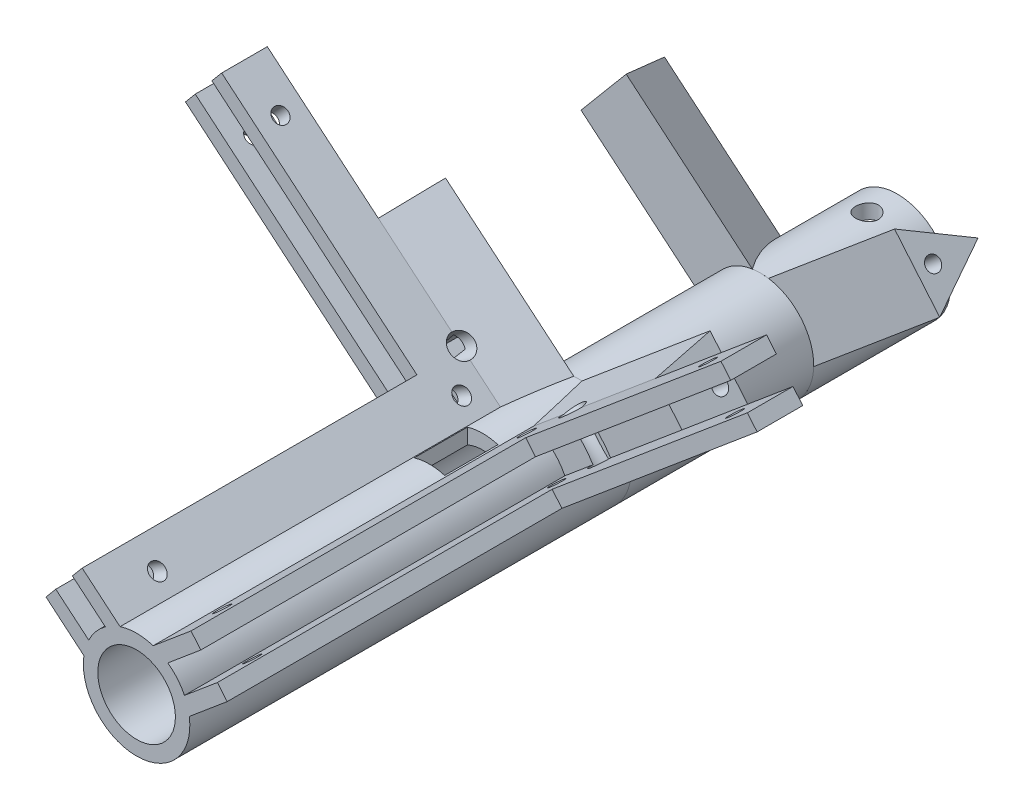
SolidWorks part; units mm, degrees
material "尼龙 101"
ref_plane "前视基准面" through (0, 0, 0) normal (0, 0, 1) x (1, 0, 0)
ref_plane "上视基准面" through (0, 0, 0) normal (0, 1, 0) x (1, 0, 0)
ref_plane "右视基准面" through (0, 0, 0) normal (1, 0, 0) x (0, 0, -1)
other "Configuration Table"
ref_plane "基准面1" through (0, 0, 10) normal (0, 0, 1) x (1, 0, 0)
sketch "草图1" plane through (0, 0, 10) normal (0, 0, 1) x (1, 0, 0)
  circle A0 centre (0, 0) radius 5.1
  circle A1 centre (0, 0) radius 7
  dimension "D1" = 10.2
  dimension "D2" = 14
extrude "凸台-拉伸1" add sketch "草图1" along normal blind 100
ref_plane "基准面2" through (0, 0, 20) normal (0, 0, 1) x (1, 0, 0)
sketch "草图2" plane through (0, 0, 20) normal (0, 0, 1) x (1, 0, 0)
  line L0 (0, -1000) -> (0, 49000) construction
  line L1 (766.0444, -642.7876) -> (-37536.1777, 31496.5929) construction
  line L2 (-766.0444, -642.7876) -> (37536.1777, 31496.5929) construction
  line L3 (0.5389, 6.9792) -> (17.3919, 21.1206)
  line L4 (6.9668, -0.6812) -> (23.8198, 13.4601)
  line L5 (17.3919, 21.1206) -> (23.8198, 13.4601)
  line L6 (-17.3919, 21.1206) -> (-23.8198, 13.4601)
  line L7 (-6.9668, -0.6812) -> (-23.8198, 13.4601)
  line L8 (-0.5389, 6.9792) -> (-17.3919, 21.1206)
  arc A0 (0.5389, 6.9792) -> (-0.5389, 6.9792) centre (0, 0) ccw
  arc A1 (-6.9668, -0.6812) -> (6.9668, -0.6812) centre (0, 0) ccw
  circle A2 centre (0, 0) radius 5.1
  dimension "D1" = 14
  dimension "D6" = 10.2
  dimension "D2" = 50
  dimension "D3" = 50
  dimension "D4" = 10
  dimension "D5" = 22
extrude "凸台-拉伸2" add sketch "草图2" along normal blind 40
ref_plane "基准面3" through (0, 0, 0) normal (-0.6428, 0.766, 0) x (0.766, 0.6428, 0)
sketch "草图4" plane through (0, 0, 0) normal (-0.6428, 0.766, 0) x (0.766, 0.6428, 0)
  line L0 (0, -1000) -> (0, 49000) construction
  line L1 (26.899, -60) -> (26.899, -20) construction
  line L2 (6.999, -28) -> (27.999, -28)
  line L3 (6.999, -28) -> (6.999, -52)
  line L4 (6.999, -52) -> (27.999, -52)
  line L5 (27.999, -28) -> (27.999, -52)
  line L6 (6.999, -28) -> (27.999, -52) construction
  line L7 (6.999, -52) -> (27.999, -28) construction
  point P1 (17.499, -40)
  point P11 (26.899, -40)
  dimension "D1" = 9.4
  dimension "D2" = 21
  dimension "D3" = 24
revolve "切除-旋转1" cut sketch "草图4" angle 360 about L0
sketch "草图5" plane through (20.6058, 17.2903, 0) normal (0.766, 0.6428, 0) x (0, 0, -1)
  circle A0 centre (-25.9, 0) radius 0.95
  circle A1 centre (-53.9, 0) radius 0.95
  dimension "D1" = 1.9
  dimension "D2" = 1.9
extrude "切除-拉伸1" cut sketch "草图5" against normal blind 5
chamfer "倒角1" distance 5 angle 60 4 edges at (-15.3933, 6.3894, 20) (-8.9654, 14.0499, 20) (8.9654, 14.0499, 20) (15.3933, 6.3894, 20) first distance on face at (-12.5817, 10.5573, 20) first distance on face at (12.5817, 10.5573, 20)
sketch "草图7" plane through (0, 0, 60) normal (0, 0, 1) x (1, 0, 0)
  line L0 (8.1483, 9.5786) -> (10.848, 6.3612)
  line L1 (10.848, 6.3612) -> (12.1503, 7.454)
  line L2 (12.1503, 7.454) -> (9.4506, 10.6713)
  line L3 (9.4506, 10.6713) -> (8.1483, 9.5786)
  line L4 (-12.1503, 7.454) -> (-9.4506, 10.6713)
  line L5 (6.9668, -0.6812) -> (23.8198, 13.4601) construction
  line L6 (23.8198, 13.4601) -> (17.3919, 21.1206) construction
  line L7 (0, -1000) -> (0, 49000) construction
  line L8 (-10.848, 6.3612) -> (-12.1503, 7.454)
  line L9 (-8.1483, 9.5786) -> (-10.848, 6.3612)
  line L10 (-9.4506, 10.6713) -> (-8.1483, 9.5786)
  dimension "D1" = 4.2
  dimension "D2" = 1.7
  dimension "D3" = 2.9
  dimension "D4" = 12.8
extrude "切除-拉伸2" cut sketch "草图7" against normal blind 10
chamfer "倒角3" distance 8 distance2 1.3 4 edges at (15.3933, 6.3894, 60) (8.9654, 14.0499, 60) (-15.3933, 6.3894, 60) (-8.9654, 14.0499, 60) first distance on face at (15.3933, 6.3894, 56) first distance on face at (8.9654, 14.0499, 56) first distance on face at (-15.3933, 6.3894, 56) first distance on face at (-8.9654, 14.0499, 56)
sketch "草图10" plane through (0, 0, 60) normal (0, 0, 1) x (1, 0, 0)
  line L0 (2.1737, 6.654) -> (32.8155, 32.3655)
  line L1 (6.9303, 0.9852) -> (37.5721, 26.6967)
  line L2 (18.2275, 20.1247) -> (2.1737, 6.654) construction
  line L3 (32.8155, 32.3655) -> (37.5721, 26.6967)
  line L4 (4.109, 5.6671) -> (34.101, 30.8334)
  line L5 (6.2945, 3.0625) -> (36.2865, 28.2288)
  line L6 (0, -1000) -> (0, 49000) construction
  line L7 (-32.8155, 32.3655) -> (-37.5721, 26.6967)
  line L8 (-6.9303, 0.9852) -> (-37.5721, 26.6967)
  line L9 (-6.2945, 3.0625) -> (-36.2865, 28.2288)
  line L10 (-4.109, 5.6671) -> (-34.101, 30.8334)
  line L11 (-2.1737, 6.654) -> (-32.8155, 32.3655)
  circle A0 centre (0, 0) radius 7
  line M6 (8.1483, 9.5786) -> (9.4506, 10.6713)
  line M7 (9.4506, 10.6713) -> (12.1503, 7.454)
  line M8 (12.1503, 7.454) -> (10.848, 6.3612)
  line M9 (10.848, 6.3612) -> (8.1483, 9.5786)
  arc M10 (2.1737, 6.654) -> (6.9303, 0.9852) centre (0, 0) cw
  line M11 (6.9303, 0.9852) -> (22.9841, 14.456)
  line M12 (22.9841, 14.456) -> (18.2275, 20.1247)
  line M13 (18.2275, 20.1247) -> (2.1737, 6.654)
  dimension "D1" = 14
  dimension "D2" = 40
  dimension "D3" = 2
  dimension "D4" = 2
extrude "凸台-拉伸4" add sketch "草图10" along normal blind 6 contours L4 M10 M9 M6 M7 M12 M13 | L4 L3 L0 M12 | L5 L1 L3 M12 | L5 M10 M11 M12 M7 M8 M9 | A0 L11 L7 L10 | A0 L9 L7 L8 | L4 M9 M7 M6 | L5 M9 M8 M7 region at (11.0592, 12.8311, 60) region at (26.1643, 25.479, 60) region at (-18.3205, 18.902, 60) region at (8.928, 9.9718, 60) region at (14.5566, 8.6631, 60) region at (29.6353, 21.3424, 60) region at (11.3706, 7.0608, 60) region at (-21.7961, 14.7599, 60)
sketch "草图11" plane through (0, 0, 66) normal (0, 0, 1) x (1, 0, 0)
  line L0 (2.1737, 6.654) -> (7.153, 10.8321)
  line L1 (32.8155, 32.3655) -> (2.1737, 6.654) construction
  line L2 (7.153, 10.8321) -> (11.9096, 5.1633)
  line L3 (6.9303, 0.9852) -> (37.5721, 26.6967) construction
  line L4 (11.9096, 5.1633) -> (6.9303, 0.9852)
  line L5 (4.109, 5.6671) -> (8.4386, 9.3)
  line L6 (4.109, 5.6671) -> (34.101, 30.8334) construction
  line L7 (6.2945, 3.0625) -> (10.624, 6.6954)
  line L8 (6.2945, 3.0625) -> (36.2865, 28.2288) construction
  line L9 (0, -1000) -> (0, 49000) construction
  line L10 (-7.153, 10.8321) -> (-11.9096, 5.1633)
  line L11 (-11.9096, 5.1633) -> (-6.9303, 0.9852)
  line L12 (-6.2945, 3.0625) -> (-10.624, 6.6954)
  line L13 (-4.109, 5.6671) -> (-8.4386, 9.3)
  line L14 (-2.1737, 6.654) -> (-7.153, 10.8321)
  circle A0 centre (0, 0) radius 7
  arc M8 (-6.9303, 0.9852) -> (-6.2945, 3.0625) centre (0, 0) cw
  line M9 (-6.2945, 3.0625) -> (-36.2865, 28.2288)
  line M11 (-37.5721, 26.6967) -> (-6.9303, 0.9852)
  dimension "D1" = 14
  dimension "D2" = 6.5
extrude "凸台-拉伸5" add sketch "草图11" along normal through all contours A0 L5 L2 L0 | A0 L4 L2 L7 | A0 L14 L10 L13 | L10 M9 M11 M8 region at (5.4733, 8.1477, 66) region at (-5.4733, 8.1477, 66) region at (8.9744, 3.9753, 66) region at (-8.9744, 3.9753, 66)
sketch "草图13" plane through (0, 0, 0) normal (-0.6428, 0.766, 0) x (0.766, 0.6428, 0)
  line L0 (12.399, -60) -> (14.099, -60) construction
  line L1 (0, -999.3806) -> (0, 49000.6194) construction
  circle A0 centre (13.249, -60) radius 1.5
  dimension "D1" = 3
revolve "切除-旋转2" cut sketch "草图13" angle 360 about L1
sketch "草图14" plane through (-20.6058, 17.2903, 0) normal (-0.766, 0.6428, 0) x (0, 0, 1)
  circle A0 centre (26.1, -0.3812) radius 0.95
  circle A1 centre (54.1, -0.3812) radius 0.95
  dimension "D1" = 1.9
  dimension "D2" = 1.9
extrude "切除-拉伸3" cut sketch "草图14" against normal blind 5
sketch "草图15" plane through (0, 0, 0) normal (0, 1, 0) x (1, 0, 0)
  line L1 (-2, -64.5) -> (2, -64.5)
  line L2 (-2, -64.5) -> (-2, -71.5)
  line L3 (-2, -71.5) -> (2, -71.5)
  line L4 (2, -64.5) -> (2, -71.5)
  line L5 (-2, -64.5) -> (2, -71.5) construction
  line L6 (-2, -71.5) -> (2, -64.5) construction
  circle A0 centre (0, -14) radius 1.5
  point P3 (0, -68)
  dimension "D1" = 3
  dimension "D2" = 4
  dimension "D3" = 7
  dimension "D4" = 68
extrude "切除-拉伸4" cut sketch "草图15" along normal through all
sketch "草图16" plane through (0, 0, 0) normal (-0.6428, 0.766, 0) x (0.766, 0.6428, 0)
  line L0 (0, -1000) -> (0, 49000) construction
  circle A0 centre (39.9422, -63) radius 1
  circle A1 centre (9.4422, -63) radius 1
  circle A2 centre (9.4422, -103) radius 1
  dimension "D1" = 2
  dimension "D2" = 2
  dimension "D3" = 2
revolve "切除-旋转3" cut sketch "草图16" angle 360 about L0
